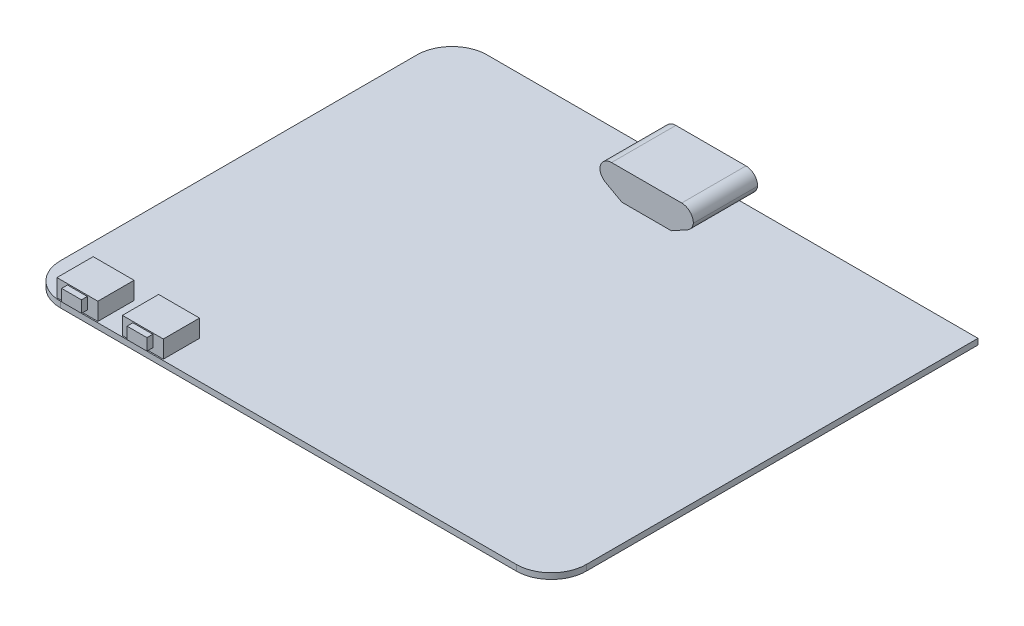
SolidWorks part; units mm, degrees
ref_plane "Спереди" through (0, 0, 0) normal (0, 0, 1) x (1, 0, 0)
ref_plane "Сверху" through (0, 0, 0) normal (0, 1, 0) x (1, 0, 0)
ref_plane "Справа" through (0, 0, 0) normal (1, 0, 0) x (0, 0, -1)
sketch "Эскиз1" plane through (0, 0, 0) normal (0, 1, 0) x (1, 0, 0)
  line L1 (-22.5, 18.25) -> (22.5, 18.25)
  line L2 (-22.5, 18.25) -> (-22.5, -18.25)
  line L3 (-22.5, -18.25) -> (22.5, -18.25)
  line L4 (22.5, 18.25) -> (22.5, -18.25)
  line L5 (-22.5, 18.25) -> (22.5, -18.25) construction
  line L6 (-22.5, -18.25) -> (22.5, 18.25) construction
  point P0 (0, 0)
  dimension "D1" = 45
  dimension "D2" = 36.5
extrude "Бобышка-Вытянуть1" add sketch "Эскиз1" along normal blind 0.5
fillet "Скругление1" radius 3 3 edges at (-22.5, 0.25, -18.25) (22.5, 0.25, 18.25) (-22.5, 0.25, 18.25)
sketch "Эскиз2" plane through (0, 0, 0) normal (0, -1, 0) x (1, 0, 0)
  line L0 (-19.5, 18.25) -> (19.5, 18.25) construction
  line L1 (-17.2, 2.95) -> (-11.4, 2.95)
  line L2 (-17.2, 2.95) -> (-17.2, -0.05)
  line L3 (-17.2, -0.05) -> (-11.4, -0.05)
  line L4 (-11.4, 2.95) -> (-11.4, -0.05)
  line L5 (-22.5, -15.25) -> (-22.5, 15.25) construction
  dimension "D1" = 5.8
  dimension "D2" = 3
  dimension "D3" = 15.3
  dimension "D4" = 5.3
extrude "Бобышка-Вытянуть2" add sketch "Эскиз2" along normal blind 1.1
sketch "Эскиз3" plane through (0, -1.1, 0) normal (0, -1, 0) x (1, 0, 0)
  line L0 (-17.2, 1.45) -> (-11.4, 1.45) construction
  line L1 (-17.2, 2.95) -> (-17.2, -0.05) construction
  line L2 (-11.4, -0.05) -> (-11.4, 2.95) construction
  line L3 (-11.4, 2.95) -> (-17.2, 2.95) construction
  line L4 (-13.66, 2.55) -> (-13.26, 2.55)
  line L5 (-13.86, 2.35) -> (-13.86, 0.55)
  line L6 (-13.66, 0.35) -> (-13.26, 0.35)
  line L7 (-13.06, 2.35) -> (-13.06, 0.55)
  line L8 (-13.86, 2.55) -> (-13.06, 0.35) construction
  line L9 (-13.86, 0.35) -> (-13.06, 2.55) construction
  arc A0 (-13.86, 0.55) -> (-13.66, 0.35) centre (-13.66, 0.55) ccw
  arc A1 (-13.26, 0.35) -> (-13.06, 0.55) centre (-13.26, 0.55) ccw
  arc A2 (-13.06, 2.35) -> (-13.26, 2.55) centre (-13.26, 2.35) ccw
  arc A3 (-13.66, 2.55) -> (-13.86, 2.35) centre (-13.66, 2.35) ccw
  circle A4 centre (-16.2, 1.45) radius 0.65
  circle A5 centre (-12.2, 1.45) radius 0.47
  point P6 (-13.46, 1.45)
  point P29 (0, 0)
  dimension "D1" = 0.2
  dimension "D7" = 1.3
  dimension "D8" = 0.94
  dimension "D2" = 1
  dimension "D3" = 0.4
  dimension "D4" = 0.4
  dimension "D5" = 3.34
  dimension "D6" = 5
extrude "Вырез-Вытянуть1" cut sketch "Эскиз3" against normal blind 0.9
fillet "Скругление2" radius 0.1 8 edges at (-13.86, -0.2, 1.45) (-13.8014, -0.2, 2.4914) (-13.46, -0.2, 2.55) (-13.1186, -0.2, 2.4914) (-13.06, -0.2, 1.45) (-13.1186, -0.2, 0.4086) (-13.46, -0.2, 0.35) (-13.8014, -0.2, 0.4086)
sketch "Эскиз4" plane through (0, 0, 0) normal (0, -1, 0) x (1, 0, 0)
  line L0 (22.5, -18.25) -> (-19.5, -18.25) construction
  line L1 (-12.5, -4.75) -> (-15.5, -4.75)
  line L2 (-12.5, -4.75) -> (-12.5, -7.75)
  line L3 (-12.5, -7.75) -> (-15.5, -7.75)
  line L4 (-15.5, -4.75) -> (-15.5, -7.75)
  line L5 (-12.5, -4.75) -> (-15.5, -7.75) construction
  line L6 (-12.5, -7.75) -> (-15.5, -4.75) construction
  line L7 (-22.5, -15.25) -> (-22.5, 15.25) construction
  point P0 (-14, -6.25)
  dimension "D1" = 3
  dimension "D2" = 3
  dimension "D3" = 10.5
  dimension "D4" = 7
extrude "Бобышка-Вытянуть3" add sketch "Эскиз4" along normal blind 0.5
sketch "Эскиз5" plane through (0, 0.5, 0) normal (0, 1, 0) x (1, 0, 0)
  line L0 (-22.5, 15.25) -> (-22.5, -15.25) construction
  line L1 (-4.7, 18.6) -> (3.3, 18.6)
  line L2 (-4.7, 18.6) -> (-4.7, 13.1)
  line L3 (-4.7, 13.1) -> (3.3, 13.1)
  line L4 (3.3, 18.6) -> (3.3, 13.1)
  line L5 (-4.7, 18.6) -> (3.3, 13.1) construction
  line L6 (-4.7, 13.1) -> (3.3, 18.6) construction
  line L7 (22.5, 18.25) -> (-19.5, 18.25) construction
  point P0 (-0.7, 15.85)
  dimension "D1" = 8
  dimension "D2" = 5.5
  dimension "D3" = 17.8
  dimension "D4" = 0.35
extrude "Бобышка-Вытянуть4" add sketch "Эскиз5" along normal blind 2.5
fillet "Скругление3" radius 1 2 edges at (-4.7, 3, -15.85) (3.3, 3, -15.85)
sketch "Эскиз6" plane through (0, 0, -13.1) normal (0, 0, 1) x (1, 0, 0)
  line L0 (1.4168, 0.5) -> (3.3, 1.5401)
  line L1 (-4.7, 0.5) -> (3.3, 0.5) construction
  line L2 (3.3, 2) -> (3.3, 0.5) construction
  line L3 (-0.7, 3) -> (-0.7, 0.5) construction
  line L4 (-3.7, 3) -> (2.3, 3) construction
  line L5 (-2.8168, 0.5) -> (-4.7, 1.5401)
  line M5 (-4.7, 2) -> (-4.7, 0.5)
  line M6 (-4.7, 0.5) -> (3.3, 0.5)
  line M7 (3.3, 0.5) -> (3.3, 2)
extrude "Вырез-Вытянуть2" cut sketch "Эскиз6" against normal through all contours L5 M6 M5 | L0 M6 M7 region at (-4.0723, 0.8467, -13.1) region at (2.6723, 0.8467, -13.1)
fillet "Скругление4" radius 1 2 edges at (3.3, 1.5401, -15.85) (-4.7, 1.5401, -15.85)
sketch "Эскиз8" plane through (0, 0, -18.6) normal (0, 0, -1) x (-1, 0, 0)
  line L8 (-2.6959, 1.4349) -> (-1.3653, 0.7)
  line L9 (-1.3653, 0.7) -> (2.7653, 0.7)
  line L10 (2.7653, 0.7) -> (4.0959, 1.4349)
  line L11 (3.7, 2.8) -> (-2.3, 2.8)
  line L12 (-2.6959, 1.4349) -> (-1.3653, 0.7)
  line L13 (-1.3653, 0.7) -> (2.7653, 0.7)
  line L14 (2.7653, 0.7) -> (4.0959, 1.4349)
  line L15 (3.7, 2.8) -> (-2.3, 2.8)
  arc A8 (-2.3, 2.8) -> (-3.0999, 2.0136) centre (-2.3, 2) ccw
  arc A9 (-3.0999, 2.0136) -> (-2.6959, 1.4349) centre (-2.3092, 2.1352) ccw
  arc A10 (4.0959, 1.4349) -> (4.4999, 2.0136) centre (3.7092, 2.1352) ccw
  arc A11 (4.4999, 2.0136) -> (3.7, 2.8) centre (3.7, 2) ccw
  arc A12 (-2.3, 2.8) -> (-3.0999, 2.0136) centre (-2.3, 2) ccw
  arc A13 (-3.0999, 2.0136) -> (-2.6959, 1.4349) centre (-2.3092, 2.1352) ccw
  arc A14 (4.0959, 1.4349) -> (4.4999, 2.0136) centre (3.7092, 2.1352) ccw
  arc A15 (4.4999, 2.0136) -> (3.7, 2.8) centre (3.7, 2) ccw
  dimension "D1" = 0.2
extrude "Вырез-Вытянуть3" cut sketch "Эскиз8" against normal blind 4.5
sketch "Эскиз9" plane through (0, 0.5, 0) normal (0, 1, 0) x (1, 0, 0)
  line L0 (-22.5, 15.25) -> (-22.5, -15.25) construction
  line L1 (-19.9, -18.15) -> (-16.4, -18.15)
  line L2 (-19.9, -18.15) -> (-19.9, -15.05)
  line L3 (-19.9, -15.05) -> (-16.4, -15.05)
  line L4 (-16.4, -18.15) -> (-16.4, -15.05)
  line L5 (-19.9, -18.15) -> (-16.4, -15.05) construction
  line L6 (-19.9, -15.05) -> (-16.4, -18.15) construction
  line L7 (-14.3, -18.15) -> (-10.8, -18.15)
  line L8 (-14.3, -18.15) -> (-14.3, -15.05)
  line L9 (-14.3, -15.05) -> (-10.8, -15.05)
  line L10 (-10.8, -18.15) -> (-10.8, -15.05)
  line L11 (-14.3, -18.15) -> (-10.8, -15.05) construction
  line L12 (-14.3, -15.05) -> (-10.8, -18.15) construction
  line L13 (-19.5, -18.25) -> (19.5, -18.25) construction
  point P0 (-18.15, -16.6)
  point P5 (-12.55, -16.6)
  dimension "D1" = 3.5
  dimension "D2" = 3.1
  dimension "D3" = 2.1
  dimension "D4" = 2.6
  dimension "D5" = 0.1
extrude "Бобышка-Вытянуть5" add sketch "Эскиз9" along normal blind 1.5
sketch "Эскиз10" plane through (0, 0, 18.15) normal (0, 0, 1) x (1, 0, 0)
  line L0 (-18.15, 2) -> (-18.15, 0.5) construction
  line L1 (-19, 1.9) -> (-17.3, 1.9)
  line L2 (-19, 1.9) -> (-19, 0.9)
  line L3 (-19, 0.9) -> (-17.3, 0.9)
  line L4 (-17.3, 1.9) -> (-17.3, 0.9)
  line L5 (-19, 1.9) -> (-17.3, 0.9) construction
  line L6 (-19, 0.9) -> (-17.3, 1.9) construction
  line L7 (-19.9, 2) -> (-16.4, 2) construction
  line L8 (-19.9, 0.5) -> (-16.4, 0.5) construction
  line L9 (-16.4, 2) -> (-14.3, 2) construction
  line L10 (-15.35, 2) -> (-15.35, 0.5) construction
  line L11 (-11.7, 0.9) -> (-13.4, 1.9) construction
  line L12 (-11.7, 1.9) -> (-13.4, 0.9) construction
  line L13 (-12.55, 2) -> (-12.55, 0.5) construction
  line L14 (-13.4, 1.9) -> (-13.4, 0.9)
  line L15 (-11.7, 0.9) -> (-13.4, 0.9)
  line L16 (-11.7, 1.9) -> (-11.7, 0.9)
  line L17 (-11.7, 1.9) -> (-13.4, 1.9)
  dimension "D1" = 1.7
  dimension "D2" = 1
  dimension "D3" = 0.1
extrude "Бобышка-Вытянуть6" add sketch "Эскиз10" along normal blind 0.5
